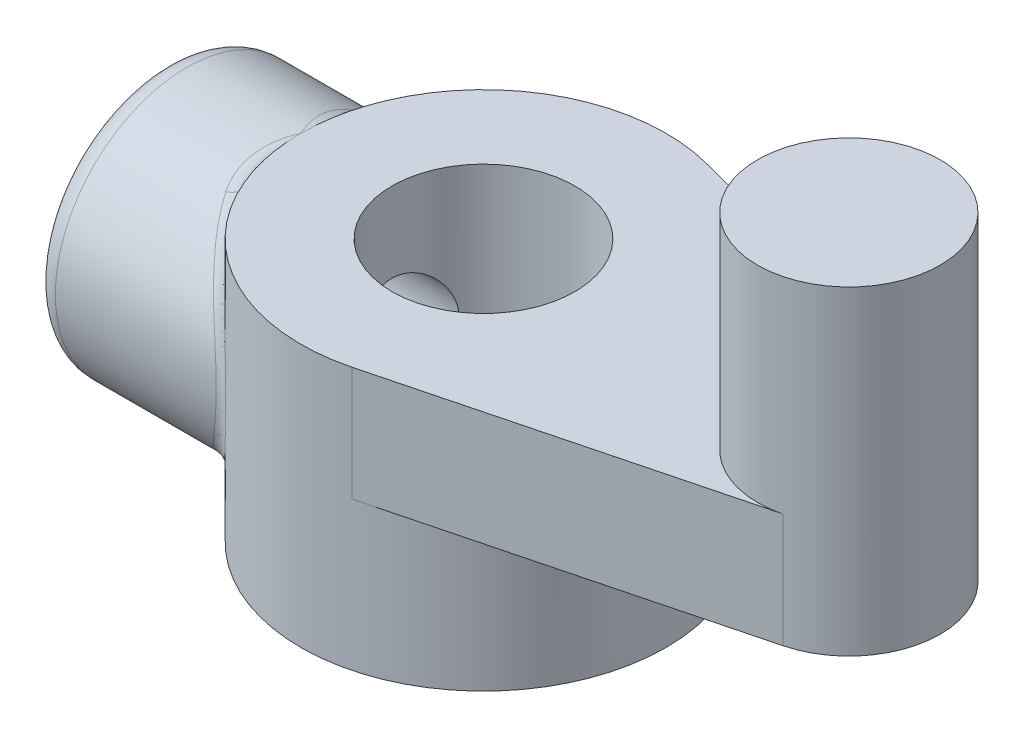
SolidWorks part; units mm, degrees
ref_plane "Front Plane" through (0, 0, 0) normal (0, 0, 1) x (1, 0, 0)
ref_plane "Top Plane" through (0, 0, 0) normal (0, 1, 0) x (1, 0, 0)
ref_plane "Right Plane" through (0, 0, 0) normal (1, 0, 0) x (0, 0, -1)
sketch "Sketch1" plane through (0, 0, 0) normal (0, 1, 0) x (1, 0, 0)
  line L0 (3.175, 12.2967) -> (26.9875, 6.1484)
  line L1 (3.175, -12.2967) -> (26.9875, -6.1484)
  circle A0 centre (0, 0) radius 12.7
  circle A1 centre (25.4, 0) radius 6.35
  circle A2 centre (0, 0) radius 6.3627
  dimension "D1" = 25.4
  dimension "D2" = 25.4
  dimension "D3" = 12.7
  dimension "D4" = 12.7254
extrude "Boss-Extrude1" add sketch "Sketch1" along normal blind 18.2562 contours A0 A2 region at (9.7563, 0, -7.5572)
extrude "Boss-Extrude2" add sketch "Sketch1<3>" against normal blind 7.9375 from surface contours A1 | A1 L0 A0 L1 region at (15.5875, 0, 0) region at (25.4, 0, 0) starting at face at (0, 18.2562, 6.3627)
sketch "Sketch1<3>" plane through (0, 0, 0) normal (0, 1, 0) x (1, 0, 0) same geometry as "Sketch1"
ref_plane "Plane1" through (-22.225, 0, 0) normal (1, 0, 0) x (0, 0, -1)
sketch "Sketch2" plane through (-22.225, 0, 0) normal (1, 0, 0) x (0, 0, -1)
  line L0 (0, 18.2562) -> (0, 0) construction
  line L1 (12.7, 18.2562) -> (-12.7, 18.2562) construction
  line L2 (-12.7, 0) -> (12.7, 0) construction
  circle A0 centre (0, 9.1281) radius 9.1281
  circle A1 centre (0, 9.1281) radius 3.5719
  dimension "D1" = 18.2562
  dimension "D2" = 7.1438
extrude "Boss-Extrude4" add sketch "Sketch2" along normal up to surface (13.3951 mm away) up to face at (0, 0, 12.7)
extrude "Cut-Extrude1" cut sketch "Sketch2<2>" along normal up to surface (16.9595 mm away) contours L0 A1 | A1 L0 region at (-22.225, 9.1281, -1.516) region at (-22.225, 9.1281, 1.516) up to face at (0, 18.2562, 6.3627)
sketch "Sketch2<2>" plane through (-22.225, 0, 0) normal (1, 0, 0) x (0, 0, -1) same geometry as "Sketch2"
fillet "Fillet1" radius 1.5875 3 edges at (-8.9745, 7.5237, -8.986) (-8.9745, 7.5237, -8.986) (-22.225, 9.1281, -9.1281)
sketch "Sketch3" plane through (0, 18.2562, 0) normal (0, 1, 0) x (1, 0, 0)
  circle A0 centre (25.4, 0) radius 6.35
  arc A1 (26.9875, -6.1484) -> (26.9875, 6.1484) centre (25.4, 0) ccw construction
extrude "Boss-Extrude5" add sketch "Sketch3" along normal blind 14.2875 contours A0
equation "\"z\"=1.3266"
equation "\"kz\"=0.1"
